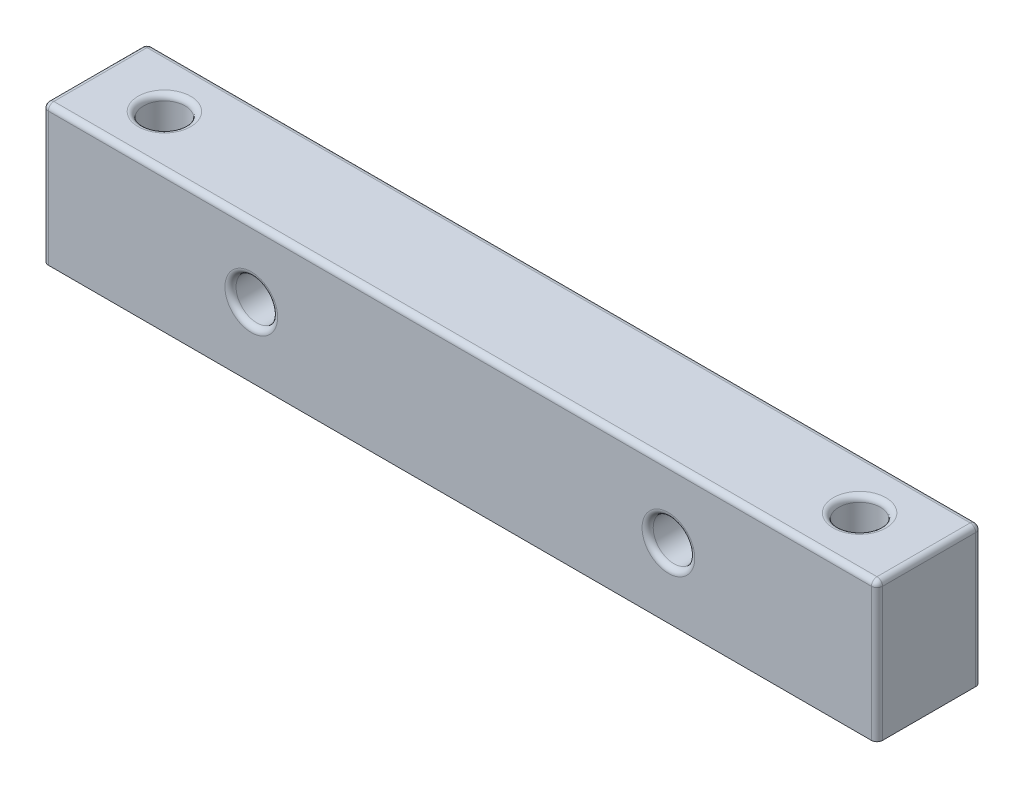
SolidWorks part; units mm, degrees
ref_plane "Front Plane" through (0, 0, 0) normal (0, 0, 1) x (1, 0, 0)
ref_plane "Top Plane" through (0, 0, 0) normal (0, 1, 0) x (1, 0, 0)
ref_plane "Right Plane" through (0, 0, 0) normal (1, 0, 0) x (0, 0, -1)
sketch "Sketch2" plane through (0, 0, 0) normal (0, 0, 1) x (1, 0, 0)
  line L1 (0, 0) -> (76.2, 0)
  line L2 (0, 0) -> (0, 12.7)
  line L3 (0, 12.7) -> (76.2, 12.7)
  line L4 (76.2, 0) -> (76.2, 12.7)
  dimension "D1" = 76.2
  dimension "D2" = 12.7
extrude "Extrude1" add sketch "Sketch2" along normal blind 9.525
hole_wizard "#10-24 Tapped Hole1" positions "3DSketch1" profile "Sketch3" tap size "#10-24" standard "Ansi Inch" end condition up to next
sketch3d "3DSketch1"
  line L0 (0, 0, 0) -> (76.2, 0, 0) construction
  line L1 (0, 0, 9.525) -> (0, 0, 0) construction
  line L2 (76.2, 0, 9.525) -> (76.2, 0, 0) construction
  point P0 (6.35, 0, 4.7625)
  point P2 (69.85, 0, 4.7625)
  dimension "D1" = 4.7625
  dimension "D2" = 6.35
  dimension "D3" = 6.35
  dimension "D4" = 4.7625
sketch "Sketch3" plane through (6.35, 0, 4.7625) normal (1, 0, 0) x (0, 0, -1)
  line L0 (0, 0) -> (0, 12.7)
  line L1 (0, 12.7) -> (1.8986, 12.7)
  line L2 (1.8986, 12.7) -> (1.8986, 0)
  line L5 (1.8986, 0) -> (0, 0)
  line L11 (0, -6.35) -> (0, 107.95) construction
  dimension "Thru Tap Drill Dia." = 3.7973
  dimension "Thru Tap Drill Depth" = 12.7
cosmetic thread "Hole Thread1" parameters "D2"=4.826
cosmetic thread "Hole Thread2" parameters "D2"=4.826
hole_wizard "#10-24 Tapped Hole2" positions "3DSketch2" profile "Sketch4" tap size "#10-24" standard "Ansi Inch" end condition up to next
sketch3d "3DSketch2"
  line L0 (0, 12.7, 9.525) -> (0, 0, 9.525) construction
  line L1 (76.2, 0, 9.525) -> (76.2, 12.7, 9.525) construction
  line L2 (0, 0, 9.525) -> (76.2, 0, 9.525) construction
  point P0 (19.05, 6.35, 9.525)
  point P2 (57.15, 6.35, 9.525)
  dimension "D1" = 19.05
  dimension "D2" = 19.05
  dimension "D3" = 6.35
  dimension "D4" = 6.35
sketch "Sketch4" plane through (19.05, 6.35, 9.525) normal (1, 0, 0) x (0, -1, 0)
  line L0 (0, 0) -> (0, 9.525)
  line L1 (0, 9.525) -> (1.8986, 9.525)
  line L2 (1.8986, 9.525) -> (1.8986, 0)
  line L5 (1.8986, 0) -> (0, 0)
  line L11 (0, -6.35) -> (0, 107.95) construction
  dimension "Thread Major Dia." = 3.7973
  dimension "Thru Tap Drill Depth" = 9.525
fillet "Fillet1" radius 0.508 14 edges at (76.2, 12.7, 4.7625) (38.1, 12.7, 9.525) (0, 12.7, 4.7625) (38.1, 12.7, 0) (69.85, 12.7, 2.8639) (6.35, 12.7, 2.8639) (0, 6.35, 9.525) (0, 6.35, 0) (76.2, 6.35, 9.525) (76.2, 6.35, 0) (17.1514, 6.35, 0) (20.9486, 6.35, 9.525) (55.2514, 6.35, 0) (59.0486, 6.35, 9.525)
